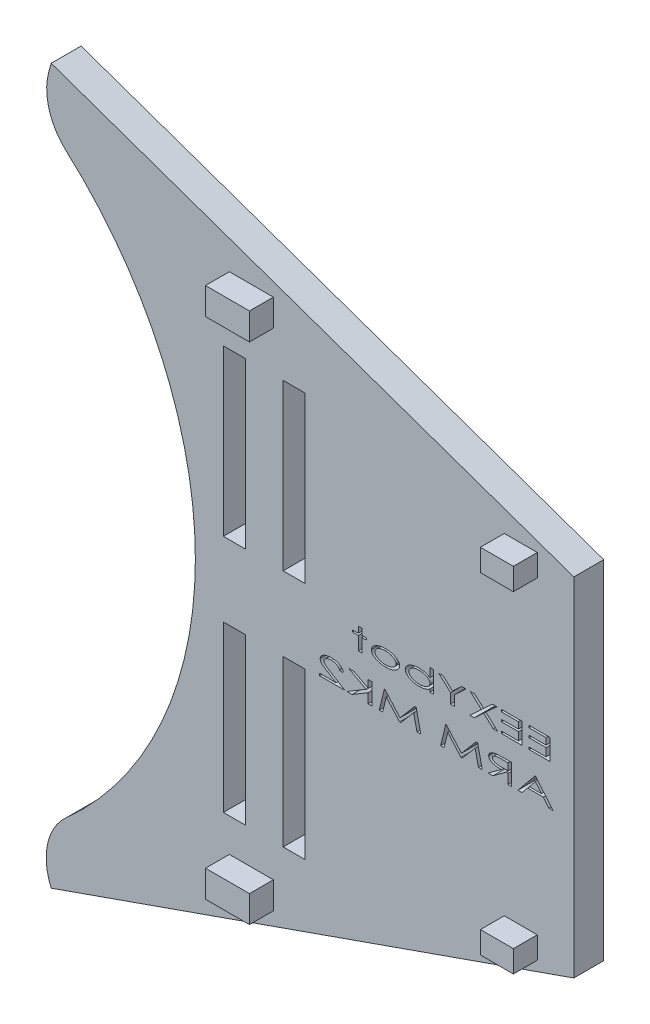
SolidWorks part; units mm, degrees
ref_plane "前视基准面" through (0, 0, 0) normal (0, 0, 1) x (1, 0, 0)
ref_plane "上视基准面" through (0, 0, 0) normal (0, 1, 0) x (1, 0, 0)
ref_plane "右视基准面" through (0, 0, 0) normal (1, 0, 0) x (0, 0, -1)
sketch "草图1" plane through (0, 0, 0) normal (0, 0, 1) x (1, 0, 0)
  line L0 (0, 0) -> (-69.4551, 0) construction
  line L1 (0, 29.0521) -> (0, -29.0521)
  line L2 (0, 29.0521) -> (-87.4257, 59.7512)
  line L3 (0, -29.0521) -> (-87.4257, -59.7512)
  line L4 (-87.4257, 59.7512) -> (-87.8068, 58.3992)
  line L5 (-87.4257, -59.7512) -> (-91.6439, -53.5511)
  arc A0 (-91.6439, -53.5511) -> (-84.8552, 48.2384) centre (-128.0781, 0) ccw
  arc A1 (-84.8552, 48.2384) -> (-87.8068, 58.3992) centre (-78.1819, 55.6861) cw
  point P9 (0, 0)
  dimension "D1" = 10
extrude "凸台-拉伸1" add sketch "草图1" along normal blind 5 contours A0 A1 L4 L2 L1 L3 L5
fillet "圆角1" radius 10 1 edges at (-91.6439, -53.5511, 2.5)
sketch "草图2" plane through (0, 0, 0) normal (0, 0, -1) x (-1, 0, 0)
  text T0 "EEXYbot\r\nARM MK2" font "Century Gothic" height 3.5
extrude "切除-拉伸1" cut sketch "草图2" against normal through all
sketch "草图3" plane through (0, 0, 0) normal (0, 0, -1) x (-1, 0, 0)
  line L0 (54.947, 33.2118) -> (54.947, 5.6205)
  line L1 (44.947, 33.2118) -> (48.6258, 33.2118)
  line L2 (44.947, 33.2118) -> (44.947, 5.6205)
  line L3 (44.947, 5.6205) -> (48.6258, 5.6205)
  line L4 (48.6258, 33.2118) -> (48.6258, 5.6205)
  line L5 (54.947, 33.2118) -> (58.6258, 33.2118)
  line L6 (58.6258, 33.2118) -> (58.6258, 5.6205)
  line L7 (54.947, 5.6205) -> (58.6258, 5.6205)
  line L8 (54.947, -6.7882) -> (54.947, -34.3795)
  line L9 (54.947, -6.7882) -> (58.6258, -6.7882)
  line L10 (58.6258, -6.7882) -> (58.6258, -34.3795)
  line L11 (54.947, -34.3795) -> (58.6258, -34.3795)
  line L12 (44.947, -6.7882) -> (44.947, -34.3795)
  line L13 (44.947, -6.7882) -> (48.6258, -6.7882)
  line L14 (48.6258, -6.7882) -> (48.6258, -34.3795)
  line L15 (44.947, -34.3795) -> (48.6258, -34.3795)
  dimension "D1" = 2
  dimension "D2" = 2
extrude "切除-拉伸2" cut sketch "草图3" against normal through all
sketch "草图5" plane through (0, 0, 5) normal (0, 0, 1) x (1, 0, 0)
  line L0 (0, 0) -> (-84.3924, 0) construction
  line L1 (-11.633, -25.8541) -> (-6.1147, -25.8541)
  line L2 (-57.6185, 44.4527) -> (-50.2608, 44.4527)
  line L3 (-57.6185, 44.4527) -> (-57.6185, 39.9564)
  line L4 (-57.6185, 39.9564) -> (-50.2608, 39.9564)
  line L5 (-50.2608, 44.4527) -> (-50.2608, 39.9564)
  line L6 (-11.633, 29.533) -> (-6.1147, 29.533)
  line L7 (-11.633, 29.533) -> (-11.633, 25.8541)
  line L8 (-11.633, 25.8541) -> (-6.1147, 25.8541)
  line L9 (-6.1147, 29.533) -> (-6.1147, 25.8541)
  line L10 (-11.633, -29.533) -> (-6.1147, -29.533)
  line L11 (-6.1147, -29.533) -> (-6.1147, -25.8541)
  line L12 (-11.633, -29.533) -> (-11.633, -25.8541)
  line L13 (-57.6185, -39.9564) -> (-50.2608, -39.9564)
  line L14 (-50.2608, -44.4527) -> (-50.2608, -39.9564)
  line L15 (-57.6185, -44.4527) -> (-50.2608, -44.4527)
  line L16 (-57.6185, -44.4527) -> (-57.6185, -39.9564)
extrude "凸台-拉伸2" add sketch "草图5" along normal blind 4
